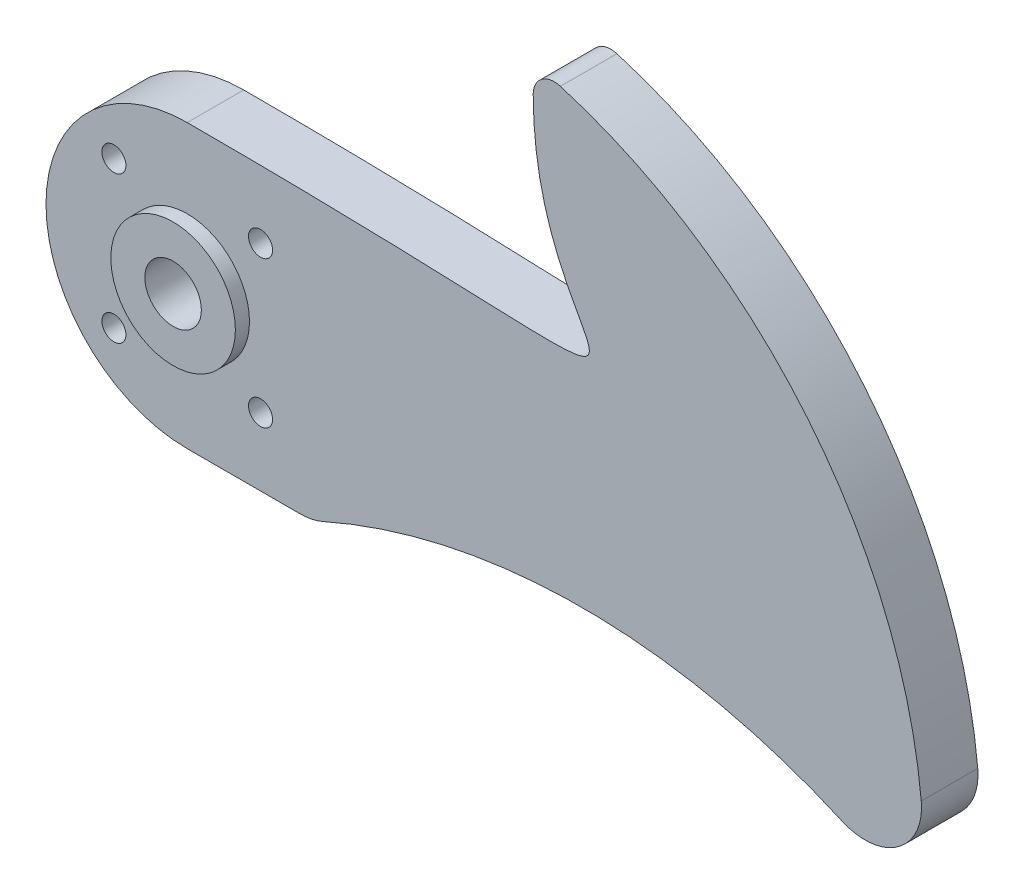
SolidWorks part; units mm, degrees
material "6061 Alloy"
ref_plane "Front" through (0, 0, 0) normal (0, 0, 1) x (1, 0, 0)
ref_plane "Top" through (0, 0, 0) normal (0, 1, 0) x (1, 0, 0)
ref_plane "Right" through (0, 0, 0) normal (1, 0, 0) x (0, 0, -1)
sketch "Sketch1" plane through (0, 0, 0) normal (0, 0, 1) x (1, 0, 0)
  line L0 (0, -15.875) -> (12.7, -15.875)
  line L2 (8.2424, 8.2424) -> (-8.2424, -8.2424) construction
  line L3 (-8.2424, 8.2424) -> (8.2424, -8.2424) construction
  line L4 (0, 0) -> (0, -43.6829) construction
  line L5 (0, -21.8415) -> (119.7815, -21.8415) construction
  line L6 (-8.2424, -51.9253) -> (8.2424, -35.4405) construction
  line L7 (8.2424, -51.9253) -> (-8.2424, -35.4405) construction
  line L8 (3.1238, -59.2475) -> (101.5979, -39.4838) construction
  line L9 (0, -27.8079) -> (101.5979, -27.8079) construction
  line L11 (-22.2168, 15.875) -> (22.2168, 15.875) construction
  line L12 (38.8937, 29.9495) -> (38.8937, 72.4954) construction
  arc A0 (0, 15.875) -> (0, -15.875) centre (0, 0) ccw
  circle A1 centre (0, 0) radius 3.175
  circle A6 centre (0, 0) radius 11.6565 construction
  circle A7 centre (8.2424, 8.2424) radius 1.3525 construction
  circle A8 centre (-8.2424, 8.2424) radius 1.3525 construction
  circle A9 centre (-8.2424, -8.2424) radius 1.3525 construction
  circle A10 centre (8.2424, -8.2424) radius 1.3525 construction
  circle A12 centre (8.2424, -35.4405) radius 1.3525 construction
  circle A13 centre (-8.2424, -35.4405) radius 1.3525 construction
  circle A14 centre (-8.2424, -51.9253) radius 1.3526 construction
  circle A15 centre (8.2424, -51.9253) radius 1.3525 construction
  circle A16 centre (0, -43.6829) radius 11.6565 construction
  arc A17 (101.5979, -27.8079) -> (101.5979, -39.4838) centre (101.5979, -33.6458) cw construction
  circle A18 centre (0, -43.6829) radius 3.175 construction
  arc A19 (3.1238, -59.2475) -> (0, -27.8079) centre (0, -43.6829) cw construction
  circle A20 centre (44.45, -21.8415) radius 25.4 construction
  arc A21 (41.9551, 40.3821) -> (82.5208, -8.9172) centre (25.6333, -14.3876) cw
  arc A25 (41.9551, 40.3821) -> (38.8937, 38.1) centre (41.275, 38.1) ccw
  arc A27 (15.2775, -15.3284) -> (73.6225, -15.3284) centre (44.45, -81.0121) cw
  circle A28 centre (44.45, -21.8415) radius 12.7 construction
  arc A29 (12.7, -15.875) -> (15.2775, -15.3284) centre (12.7, -9.525) ccw
  arc A30 (73.6225, -15.3284) -> (82.5208, -8.9172) centre (76.2, -9.525) ccw
  spline S0 degree 3 poles (38.8937, 38.1) (38.8937, 8.2406) (68.3426, 15.875) (0, 15.875) knots 0 0 0 0 1 1 1 1
  dimension "D1" = 6.35
  dimension "D2" = 31.75
  dimension "D3" = 6.35
  dimension "D4" = 57.15
  dimension "D5" = 43.6829
  dimension "D6" = 50.8
  dimension "D7" = 23.313
  dimension "D8" = 2.7051
  dimension "D10" = 82.55
  dimension "D11" = 63.5
  dimension "D12" = 4.7625
  dimension "D13" = 89.5781
  dimension "D14" = 205.0277
  dimension "D16" = 34.925
  dimension "D17" = 25.4
  dimension "D9" = 38.1
extrude "Boss-Extrude1" add sketch "Sketch1" along normal blind 6.35
hole_wizard "#6-32 Tapped Hole1" positions "Sketch2" profile "Sketch3" tap size "#6-32" standard "ANSI Inch" end condition through all
sketch "Sketch2" plane through (0, 0, 6.35) normal (0, 0, 1) x (1, 0, 0)
  point P0 (8.2424, 8.2424)
  point P3 (-8.2424, 8.2424)
  point P6 (8.2424, -8.2424)
  point P9 (-8.2424, -8.2424)
sketch "Sketch3" plane through (8.2424, 8.2424, 6.35) normal (1, 0, 0) x (0, -1, 0)
  line L0 (0, 0) -> (0, 6.35)
  line L1 (0, 6.35) -> (1.3525, 6.35)
  line L2 (1.3525, 6.35) -> (1.3525, 0)
  line L5 (1.3525, 0) -> (0, 0)
  line L11 (0, -6.35) -> (0, 107.95) construction
  dimension "Thru Tap Drill Dia." = 2.7051
  dimension "Thru Tap Drill Depth" = 6.35
sketch "Sketch4" plane through (0, 0, 6.35) normal (0, 0, 1) x (1, 0, 0)
  circle A0 centre (0, 0) radius 3.175
  circle A1 centre (0, 0) radius 7
  dimension "D1" = 6.35
  dimension "D2" = 14
extrude "Boss-Extrude2" add sketch "Sketch4" along normal blind 1.5875
sketch "Sketch5" [suppressed] plane through (0, 0, 0) normal (0, 0, -1) x (-1, 0, 0)
  circle A0 centre (0, 0) radius 7
  circle A2 centre (0, 0) radius 3.175 construction
  circle A3 centre (0, 0) radius 3.175
  dimension "D2" = 14
extrude "Boss-Extrude3" [suppressed] add sketch "Sketch5" along normal blind 1.5875
sketch "Sketch6" plane through (0, 0, 6.35) normal (0, 0, 1) x (1, 0, 0)
  line L0 (68.326, -15.419) -> (72.3338, -12.2975)
  line L1 (72.3338, -12.2975) -> (73.0332, -17.3291)
  line L2 (68.326, -15.419) -> (73.0332, -17.3291)
  line L3 (72.3338, -12.2975) -> (71.4742, -14.4157) construction
  line L4 (70.2513, -13.9194) -> (72.6972, -14.912) construction
  circle A0 centre (44.45, -81.0121) radius 71.8706 construction
  arc A1 (73.6225, -15.3284) -> (82.5208, -8.9172) centre (76.2, -9.525) ccw construction
  arc A2 (73.6225, -15.3284) -> (15.2775, -15.3284) centre (44.45, -81.0121) ccw construction
  point P10 (71.4742, -14.4157)
  dimension "D1" = 2.286
  dimension "D2" = 2.54
  dimension "D3" = 5.08
extrude "Cut-Extrude1" [suppressed] cut sketch "Sketch6" against normal through all and the other way through all
pattern_curve "CrvPattern1" [suppressed] of bodies 113 parameters "D1"=25, "D3"=50, "D2"=1, "D4"=50
